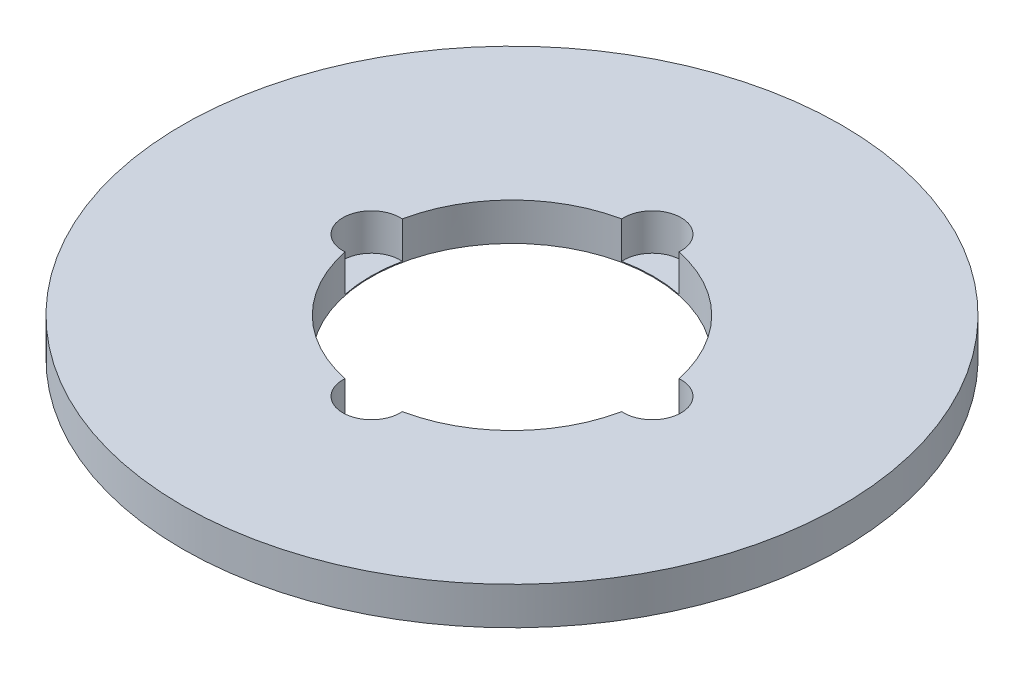
SolidWorks part; units mm, degrees
ref_plane "Front Plane" through (0, 0, 0) normal (0, 0, 1) x (1, 0, 0)
ref_plane "Top Plane" through (0, 0, 0) normal (0, 1, 0) x (1, 0, 0)
ref_plane "Right Plane" through (0, 0, 0) normal (1, 0, 0) x (0, 0, -1)
sketch "Sketch1" plane through (0, 0, 0) normal (0, 1, 0) x (1, 0, 0)
  circle A0 centre (0, 0) radius 35
  dimension "FLANGE_OD" = 70
extrude "Boss-Extrude1" add sketch "Sketch1" along normal blind 4
sketch "Sketch2" plane through (0, 0, 0) normal (0, 1, 0) x (1, 0, 0)
  circle A0 centre (0, 0) radius 15
  dimension "BORE_D" = 30
extrude "Cut-Extrude1" cut sketch "Sketch2" along normal through all
sketch "Sketch3" plane through (0, 4, 0) normal (0, 1, 0) x (1, 0, 0)
  circle A0 centre (0, 0) radius 14.9127 construction
  circle A1 centre (-14.9127, 0) radius 3.0462
  dimension "BOLT_D" = 6.0925
  dimension "BOLT_PCD" = 29.8253
extrude "Cut-Extrude2" cut sketch "Sketch3" against normal blind 3.904
pattern_circular "CirPattern1" count 4 over 360 about axis through (0, 0, 0) along (0, 1, 0) of "Cut-Extrude2"
